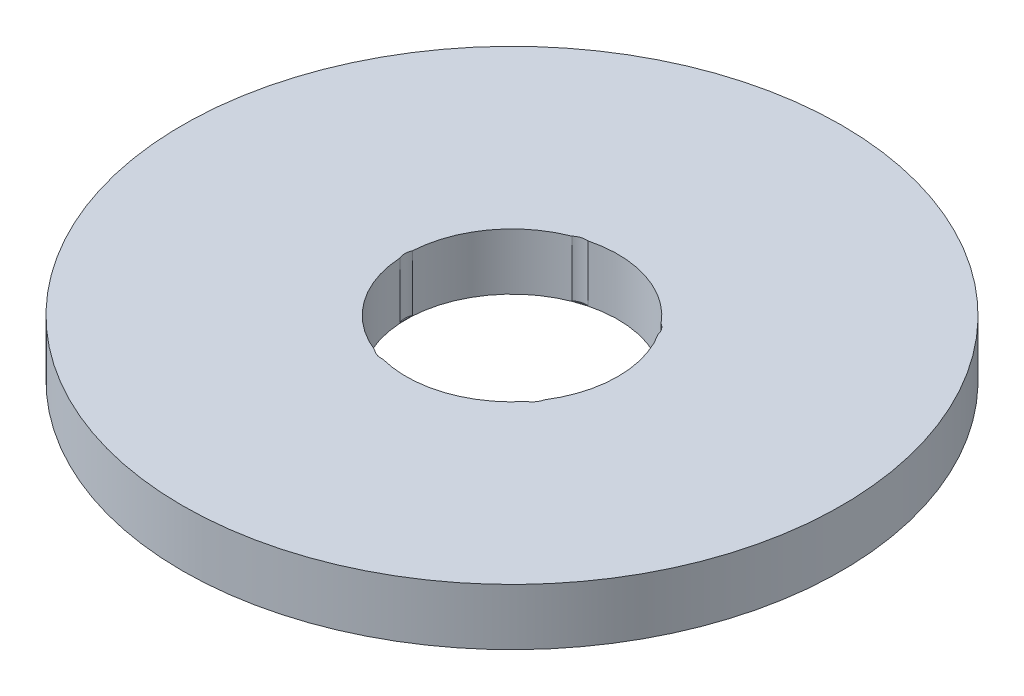
SolidWorks part; units mm, degrees
ref_plane "Front Plane" through (0, 0, 0) normal (0, 0, 1) x (1, 0, 0)
ref_plane "Top Plane" through (0, 0, 0) normal (0, 1, 0) x (1, 0, 0)
ref_plane "Right Plane" through (0, 0, 0) normal (1, 0, 0) x (0, 0, -1)
sketch "Sketch1" plane through (0, 0, 0) normal (0, 1, 0) x (1, 0, 0)
  circle A0 centre (0, 0) radius 70
  dimension "FLANGE_OD" = 140
extrude "Boss-Extrude1" add sketch "Sketch1" along normal blind 12
sketch "Sketch2" plane through (0, 0, 0) normal (0, 1, 0) x (1, 0, 0)
  circle A0 centre (0, 0) radius 22.5
  dimension "BORE_D" = 45
extrude "Cut-Extrude1" cut sketch "Sketch2" along normal through all
sketch "Sketch3" plane through (0, 12, 0) normal (0, 1, 0) x (1, 0, 0)
  circle A0 centre (0, 0) radius 19.3854 construction
  circle A1 centre (-19.3854, 0) radius 3.357
  dimension "BOLT_D" = 6.714
  dimension "BOLT_PCD" = 38.7708
extrude "Cut-Extrude2" cut sketch "Sketch3" against normal blind 11.9129
pattern_circular "CirPattern1" count 5 over 360 about axis through (0, 0, 0) along (0, 1, 0) of "Cut-Extrude2"
